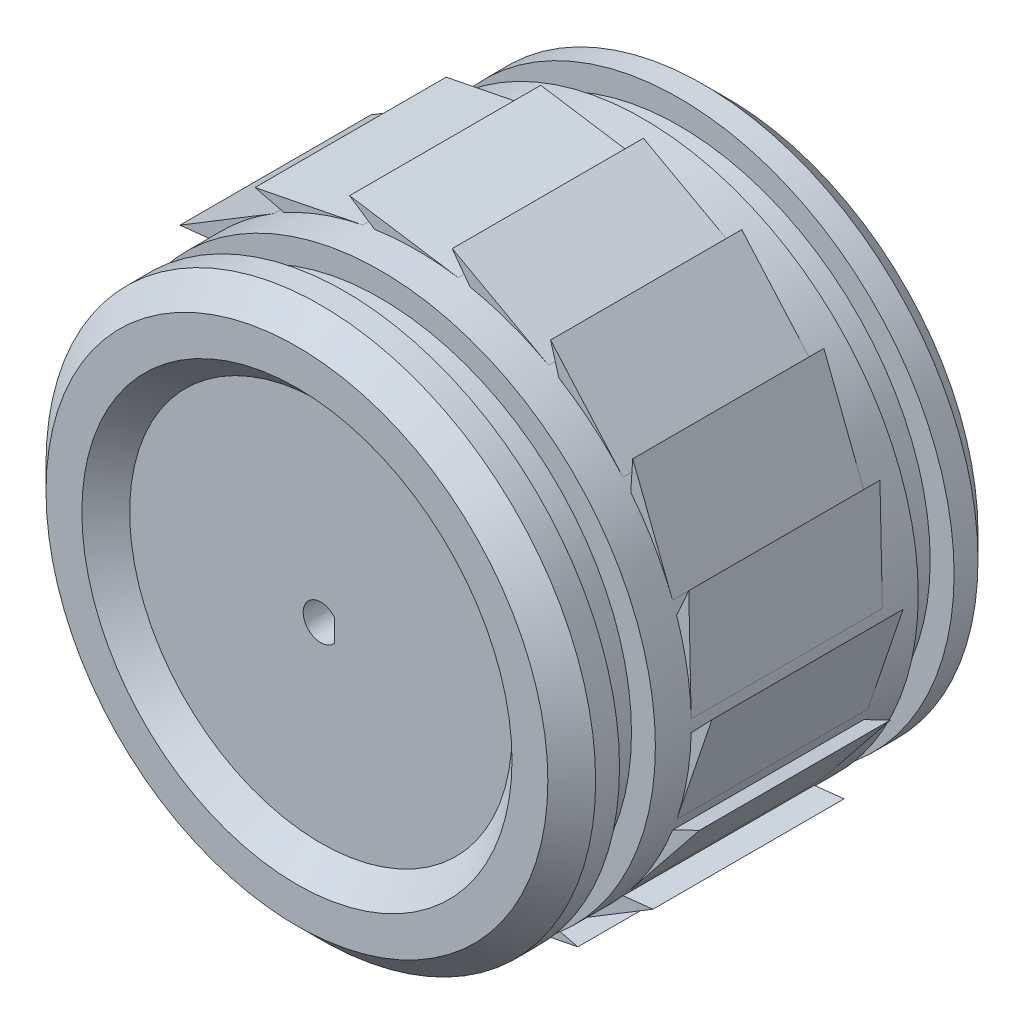
SolidWorks part; units mm, degrees
material "ABS"
ref_plane "Спереди" through (0, 0, 0) normal (0, 0, 1) x (1, 0, 0)
ref_plane "Сверху" through (0, 0, 0) normal (0, 1, 0) x (1, 0, 0)
ref_plane "Справа" through (0, 0, 0) normal (1, 0, 0) x (0, 0, -1)
sketch "Эскиз1" plane through (0, 0, 0) normal (1, 0, 0) x (0, 0, -1)
  line L0 (0, 22.5472) -> (0, -23.5635) construction
  line L1 (0, 23) -> (-16, 23)
  line L2 (-18, 21) -> (-18, 18)
  line L5 (-16, 16) -> (-16, 0)
  line L9 (16, 23) -> (0, 23)
  line L10 (-28.6739, 0) -> (34.4859, 0) construction
  line L11 (-18, 18) -> (-16, 16)
  line L12 (18, 21) -> (16, 23)
  line L14 (-16, 0) -> (-14.3343, 0)
  line L15 (-12, 10) -> (-12, 13.5)
  line L16 (-8, 17.5) -> (18, 17.5)
  line L17 (18, 17.5) -> (18, 21)
  line L19 (-16, 23) -> (-18, 21)
  line L20 (-12, 13.5) -> (-8, 17.5)
  line L21 (-16, 16) -> (-18, 16) construction
  line L22 (-14.3343, 0) -> (-6, 0)
  line L25 (-6, 0) -> (-6, 4)
  line L26 (-18, 16) -> (-18, 23) construction
  line L27 (-18, 23) -> (-16, 23) construction
  line L28 (16, 23) -> (18, 23) construction
  line L29 (18, 23) -> (18, 21) construction
  spline S0 degree 3 poles (-12, 10) (-11.4864, 10) (-7.5212, 9.1569) (-6, 5.0213) (-6, 4) knots 0 0 0 0 0.351629 1 1 1 1
  point P4 (-18, 23)
  point P6 (-18, 16)
  point P10 (-12, 17.5)
  point P11 (18, 23)
  point P21 (0, 0)
  point P29 (-6, 3.2854)
  dimension "D1" = 35
  dimension "D2" = 4
  dimension "D4" = 20
  dimension "D5" = 6
  dimension "D9" = 3
  dimension "D8" = 36
  dimension "D11" = 46
  dimension "D12" = 18
  dimension "D13" = 7
  dimension "D14" = 8
ref_axis "Ось1" through (0, 0, -80.9) along (0, 0, 1)
revolve "Повернуть1" add sketch "Эскиз1" angle 360 about L10 region at (0, 22.5728, -8)
sketch "Эскиз2" plane through (0, 0, 16) normal (0, 0, 1) x (1, 0, 0)
  line L0 (1.125, 0.9539) -> (1.125, -0.9539)
  circle A0 centre (0, 0) radius 1.475
  point P5 (-1.475, 0)
  dimension "D1" = 2.95
  dimension "D2" = 2.6
extrude "Вырез-Вытянуть1" cut sketch "Эскиз2" against normal through all contours L0 A0 region at (-0.0907, 0, 16)
ref_plane "Плоскость1" through (0, 20, 0) normal (0, 1, 0) x (1, 0, 0)
sketch "Эскиз3" plane through (0, 0, 0) normal (1, 0, 0) x (0, 0, -1)
  line L0 (-27.6376, 0) -> (18.0085, 0) construction
  line L1 (18, 21) -> (16, 23)
  line L2 (16, 23) -> (14, 23)
  line L3 (16, 23) -> (-16, 23) construction
  line L4 (14, 23) -> (14, 21)
  line L5 (14, 21) -> (11, 21)
  line L6 (11, 21) -> (11, 23)
  line L7 (11, 23) -> (-11, 23)
  line L8 (-11, 23) -> (-11, 21)
  line L9 (-11, 21) -> (-14, 21)
  line L10 (-14, 21) -> (-14, 23)
  line L11 (-14, 23) -> (-16, 23)
  line L12 (-16, 23) -> (-18, 21)
  line L13 (-18, 21) -> (-18, 24.3347)
  line L14 (-18, 24.3347) -> (18, 24.3347)
  line L15 (18, 24.3347) -> (18, 21)
  dimension "D1" = 2
  dimension "D2" = 2
  dimension "D3" = 3
  dimension "D4" = 3
  dimension "D5" = 2
revolve "Вырез-Повернуть1" cut sketch "Эскиз3" angle 360 about L0
sketch "Эскиз4" plane through (0, 0, 0) normal (0, 0, 1) x (1, 0, 0)
  line L0 (0, 25.4704) -> (0, -25.2707) construction
  line L1 (-3.5, 22.7321) -> (-5.5929, 24.1321)
  line L2 (-5.5929, 24.1321) -> (3.5, 22.7321)
  line L3 (2.9981, 24.5897) -> (11.0638, 20.1641)
  line L4 (4.4859, 22.5583) -> (2.9981, 24.5897)
  line L5 (11.2275, 22.0813) -> (17.2931, 15.1641)
  line L6 (11.9308, 19.6636) -> (11.2275, 22.0813)
  line L7 (18.1026, 16.9096) -> (21.4366, 8.335)
  line L8 (17.9366, 14.3972) -> (18.1026, 16.9096)
  line L9 (22.7943, 9.6984) -> (22.9946, 0.5006)
  line L10 (21.779, 7.3942) -> (22.7943, 9.6984)
  line L11 (24.7367, 1.3174) -> (21.779, -7.3942)
  line L12 (22.9946, -0.5006) -> (24.7367, 1.3174)
  line L13 (23.6955, -7.2225) -> (17.9366, -14.3972)
  line L14 (21.4366, -8.335) -> (23.6955, -7.2225)
  line L15 (19.7962, -14.8913) -> (11.9308, -19.6636)
  line L16 (17.2931, -15.1641) -> (19.7962, -14.8913)
  line L17 (13.5092, -20.7639) -> (4.4859, -22.5583)
  line L18 (11.0638, -20.1641) -> (13.5092, -20.7639)
  line L19 (5.5929, -24.1321) -> (-3.5, -22.7321)
  line L20 (3.5, -22.7321) -> (5.5929, -24.1321)
  line L21 (-2.9981, -24.5897) -> (-11.0638, -20.1641)
  line L22 (-4.4859, -22.5583) -> (-2.9981, -24.5897)
  line L23 (-11.2275, -22.0813) -> (-17.2931, -15.1641)
  line L24 (-11.9308, -19.6636) -> (-11.2275, -22.0813)
  line L25 (-18.1026, -16.9096) -> (-21.4366, -8.335)
  line L26 (-17.9366, -14.3972) -> (-18.1026, -16.9096)
  line L27 (-22.7943, -9.6984) -> (-22.9946, -0.5006)
  line L28 (-21.779, -7.3942) -> (-22.7943, -9.6984)
  line L29 (-24.7367, -1.3174) -> (-21.779, 7.3942)
  line L30 (-22.9946, 0.5006) -> (-24.7367, -1.3174)
  line L31 (-23.6955, 7.2225) -> (-17.9366, 14.3972)
  line L32 (-21.4366, 8.335) -> (-23.6955, 7.2225)
  line L33 (-19.7962, 14.8913) -> (-11.9308, 19.6636)
  line L34 (-17.2931, 15.1641) -> (-19.7962, 14.8913)
  line L35 (-13.5092, 20.7639) -> (-4.4859, 22.5583)
  line L36 (-11.0638, 20.1641) -> (-13.5092, 20.7639)
  arc A0 (3.5, 22.7321) -> (-3.5, 22.7321) centre (0, 0) ccw
  arc A1 (11.0638, 20.1641) -> (4.4859, 22.5583) centre (0, 0) ccw
  circle A2 centre (0, 0) radius 23 construction
  arc A3 (17.2931, 15.1641) -> (11.9308, 19.6636) centre (0, 0) ccw
  arc A4 (21.4366, 8.335) -> (17.9366, 14.3972) centre (0, 0) ccw
  arc A5 (22.9946, 0.5006) -> (21.779, 7.3942) centre (0, 0) ccw
  arc A6 (21.779, -7.3942) -> (22.9946, -0.5006) centre (0, 0) ccw
  arc A7 (17.9366, -14.3972) -> (21.4366, -8.335) centre (0, 0) ccw
  arc A8 (11.9308, -19.6636) -> (17.2931, -15.1641) centre (0, 0) ccw
  arc A9 (4.4859, -22.5583) -> (11.0638, -20.1641) centre (0, 0) ccw
  arc A10 (-3.5, -22.7321) -> (3.5, -22.7321) centre (0, 0) ccw
  arc A11 (-11.0638, -20.1641) -> (-4.4859, -22.5583) centre (0, 0) ccw
  arc A12 (-17.2931, -15.1641) -> (-11.9308, -19.6636) centre (0, 0) ccw
  arc A13 (-21.4366, -8.335) -> (-17.9366, -14.3972) centre (0, 0) ccw
  arc A14 (-22.9946, -0.5006) -> (-21.779, -7.3942) centre (0, 0) ccw
  arc A15 (-21.779, 7.3942) -> (-22.9946, 0.5006) centre (0, 0) ccw
  arc A16 (-17.9366, 14.3972) -> (-21.4366, 8.335) centre (0, 0) ccw
  arc A17 (-11.9308, 19.6636) -> (-17.2931, 15.1641) centre (0, 0) ccw
  arc A18 (-4.4859, 22.5583) -> (-11.0638, 20.1641) centre (0, 0) ccw
  point P63 (0, 0)
  dimension "D1" = 7
  dimension "D2" = 1.4
  dimension "D3" = 18
extrude "Бобышка-Вытянуть1" add sketch "Эскиз4" along normal mid plane 16
equation "\"D2@Эскиз3\"=\"D1@Эскиз3\""
equation "\"D4@Эскиз3\"=\"D3@Эскиз3\""
